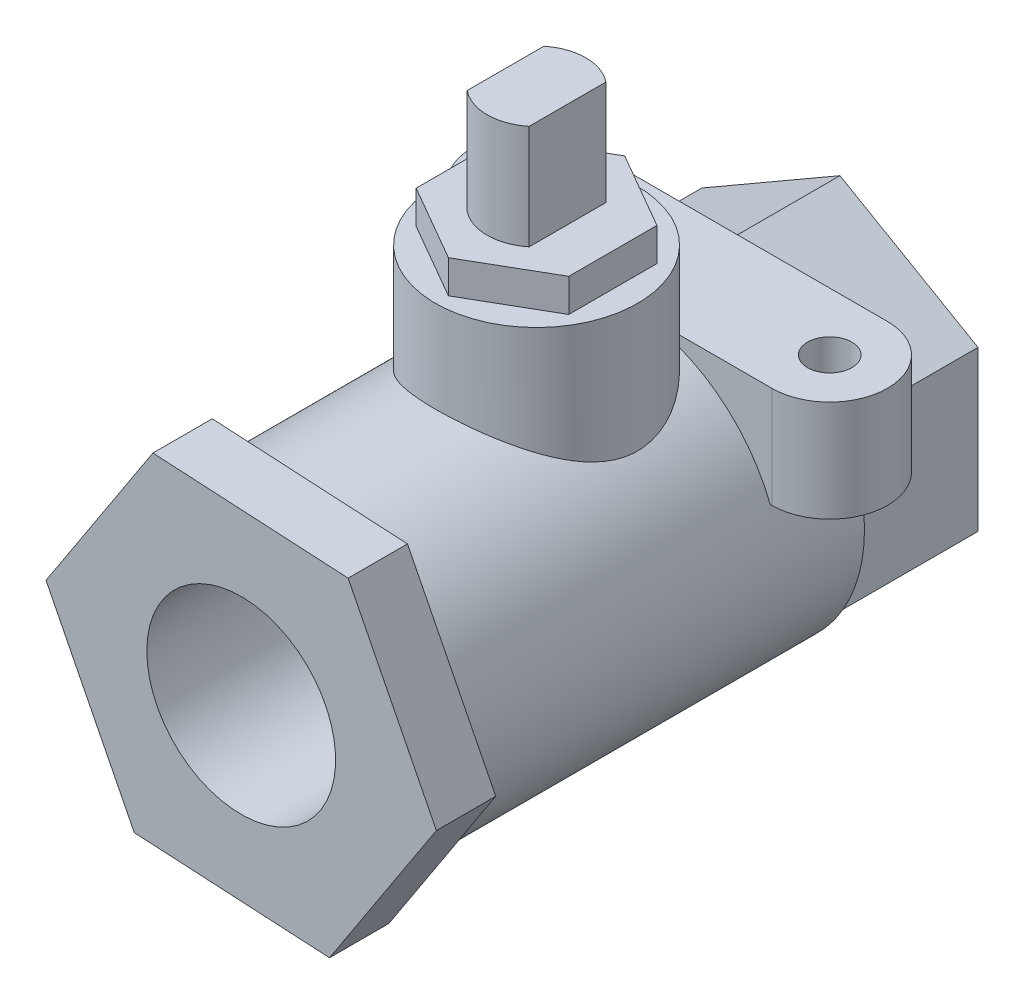
SolidWorks part; units mm, degrees
material "Cast Stainless Steel"
ref_plane "Front Plane" through (0, 0, 0) normal (0, 0, 1) x (1, 0, 0)
ref_plane "Top Plane" through (0, 0, 0) normal (0, 1, 0) x (1, 0, 0)
ref_plane "Right Plane" through (0, 0, 0) normal (1, 0, 0) x (0, 0, -1)
sketch "Sketch1" plane through (0, 0, 0) normal (0, 0, 1) x (1, 0, 0)
  circle A0 centre (0, 0) radius 15.0114
  dimension "D1" = 30.0228
extrude "Boss-Extrude1" add sketch "Sketch1" along normal blind 38.1
sketch "Sketch2" plane through (0, 0, 38.1) normal (0, 0, 1) x (1, 0, 0)
  line L1 (-8.3145, 16.4272) -> (-18.3836, 1.0131)
  line L2 (-18.3836, 1.0131) -> (-10.0691, -15.4142)
  line L3 (-10.0691, -15.4142) -> (8.3145, -16.4272)
  line L4 (8.3145, -16.4272) -> (18.3836, -1.0131)
  line L5 (18.3836, -1.0131) -> (10.0691, 15.4142)
  line L6 (10.0691, 15.4142) -> (-8.3145, 16.4272)
  circle A0 centre (0, 0) radius 15.9448 construction
  dimension "D1" = 31.8897
extrude "Boss-Extrude2" add sketch "Sketch2" along normal blind 5.588
sketch "Sketch3" plane through (0, 0, 0) normal (0, 0, -1) x (-1, 0, 0)
  line L1 (0, 15.0114) -> (-13.0003, 7.5057)
  line L2 (-13.0003, 7.5057) -> (-13.0003, -7.5057)
  line L3 (-13.0003, -7.5057) -> (0, -15.0114)
  line L4 (0, -15.0114) -> (13.0003, -7.5057)
  line L5 (13.0003, -7.5057) -> (13.0003, 7.5057)
  line L6 (13.0003, 7.5057) -> (0, 15.0114)
  circle A0 centre (0, 0) radius 13.0003 construction
  circle A1 centre (0, 0) radius 15.0114 construction
extrude "Boss-Extrude3" add sketch "Sketch3" along normal blind 12.7
ref_plane "Plane1" through (0, 15.0114, 0) normal (0, 1, 0) x (1, 0, 0)
sketch "Sketch5" plane through (0, 15.0114, 0) normal (0, 1, 0) x (1, 0, 0)
  line L0 (-14.1351, -2.4003) -> (14.1351, -2.4003) construction
  line L1 (-14.1351, 3.048) -> (14.1351, 3.048)
  line L2 (-14.1351, -7.8486) -> (14.1351, -7.8486)
  line L3 (-13.0003, 12.7) -> (0, 12.7) construction
  arc A0 (-14.1351, 3.048) -> (-14.1351, -7.8486) centre (-14.1351, -2.4003) ccw
  arc A1 (14.1351, -7.8486) -> (14.1351, 3.048) centre (14.1351, -2.4003) ccw
  point P2 (0, -2.4003)
  dimension "D3" = 28.2702
  dimension "D1" = 9.652
  dimension "D2" = 10.8966
extrude "Boss-Extrude4" add sketch "Sketch5" against normal blind 9.5504
sketch "Sketch4" plane through (0, 0, -12.7) normal (0, 0, -1) x (-1, 0, 0)
  circle A0 centre (0, 0) radius 8.89
  dimension "D1" = 17.78
extrude "Cut-Extrude1" cut sketch "Sketch4" against normal through all
sketch "Sketch6" plane through (0, 15.0114, 0) normal (0, 1, 0) x (1, 0, 0)
  line L0 (0, 12.7) -> (13.0003, 12.7) construction
  circle A0 centre (0, -15.875) radius 9.525
  dimension "D1" = 19.05
  dimension "D2" = 28.575
extrude "Boss-Extrude5" add sketch "Sketch6" along normal blind 8.636 and the other way blind 5.08
sketch "Sketch7" plane through (0, 23.6474, 0) normal (0, 1, 0) x (1, 0, 0)
  line L1 (0, -7.5748) -> (-7.1882, -11.7249)
  line L2 (-7.1882, -11.7249) -> (-7.1882, -20.0251)
  line L3 (-7.1882, -20.0251) -> (0, -24.1752)
  line L4 (0, -24.1752) -> (7.1882, -20.0251)
  line L5 (7.1882, -20.0251) -> (7.1882, -11.7249)
  line L6 (7.1882, -11.7249) -> (0, -7.5748)
  circle A0 centre (0, -15.875) radius 7.1882 construction
  dimension "D1" = 14.3764
extrude "Boss-Extrude6" add sketch "Sketch7" along normal blind 3.1115
sketch "Sketch8" plane through (0, 26.7589, 0) normal (0, 1, 0) x (1, 0, 0)
  line L1 (-2.921, -19.4907) -> (2.921, -19.4907)
  line L2 (-2.921, -19.4907) -> (-2.921, -12.2593)
  line L3 (-2.921, -12.2593) -> (2.921, -12.2593)
  line L4 (2.921, -19.4907) -> (2.921, -12.2593)
  line L5 (-2.921, -19.4907) -> (2.921, -12.2593) construction
  line L6 (-2.921, -12.2593) -> (2.921, -19.4907) construction
  circle A0 centre (0, -15.875) radius 4.6482
  circle A1 centre (0, -15.875) radius 9.525
  circle A2 centre (0, -15.875) radius 9.525 construction
  dimension "D3" = 9.2964
  dimension "D2" = 5.842
  dimension "D1" = 0
extrude "Boss-Extrude7" add sketch "Sketch8" along normal blind 9.8298 contours L1 L4 L3 L2 | L3 A0 | L1 A0 region at (0, 26.7589, 15.875) region at (0, 26.7589, 19.9079) region at (0, 26.7589, 11.8421)
sketch "Sketch9" plane through (0, 15.0114, 0) normal (0, 1, 0) x (1, 0, 0)
  line L4 (5.1286, -7.8486) -> (14.1351, -7.8486)
  line L5 (14.1351, 3.048) -> (0, 3.048)
  line L6 (0, 3.048) -> (-14.1351, 3.048)
  line L7 (-14.1351, -7.8486) -> (-5.1286, -7.8486)
  line L8 (5.1286, -7.8486) -> (14.1351, -7.8486)
  line L9 (14.1351, 3.048) -> (0, 3.048)
  line L10 (0, 3.048) -> (-14.1351, 3.048)
  line L11 (-14.1351, -7.8486) -> (-5.1286, -7.8486)
  circle A0 centre (-14.1351, -2.4003) radius 2.0892
  circle A1 centre (14.1351, -2.4003) radius 2.0891
  arc A3 (5.1286, -7.8486) -> (-5.1286, -7.8486) centre (0, -15.875) ccw
  arc A4 (14.1351, -7.8486) -> (14.1351, 3.048) centre (14.1351, -2.4003) ccw
  arc A5 (-14.1351, 3.048) -> (-14.1351, -7.8486) centre (-14.1351, -2.4003) ccw
  arc A6 (5.1286, -7.8486) -> (-5.1286, -7.8486) centre (0, -15.875) ccw
  arc A7 (14.1351, -7.8486) -> (14.1351, 3.048) centre (14.1351, -2.4003) ccw
  arc A8 (-14.1351, 3.048) -> (-14.1351, -7.8486) centre (-14.1351, -2.4003) ccw
  dimension "D2" = 4.1783
  dimension "D1" = 0
extrude "Cut-Extrude2" cut sketch "Sketch9" against normal blind 8.89 contours A1 | A0 region at (-14.1351, 15.0114, 2.4003) region at (14.1351, 15.0114, 2.4003)
